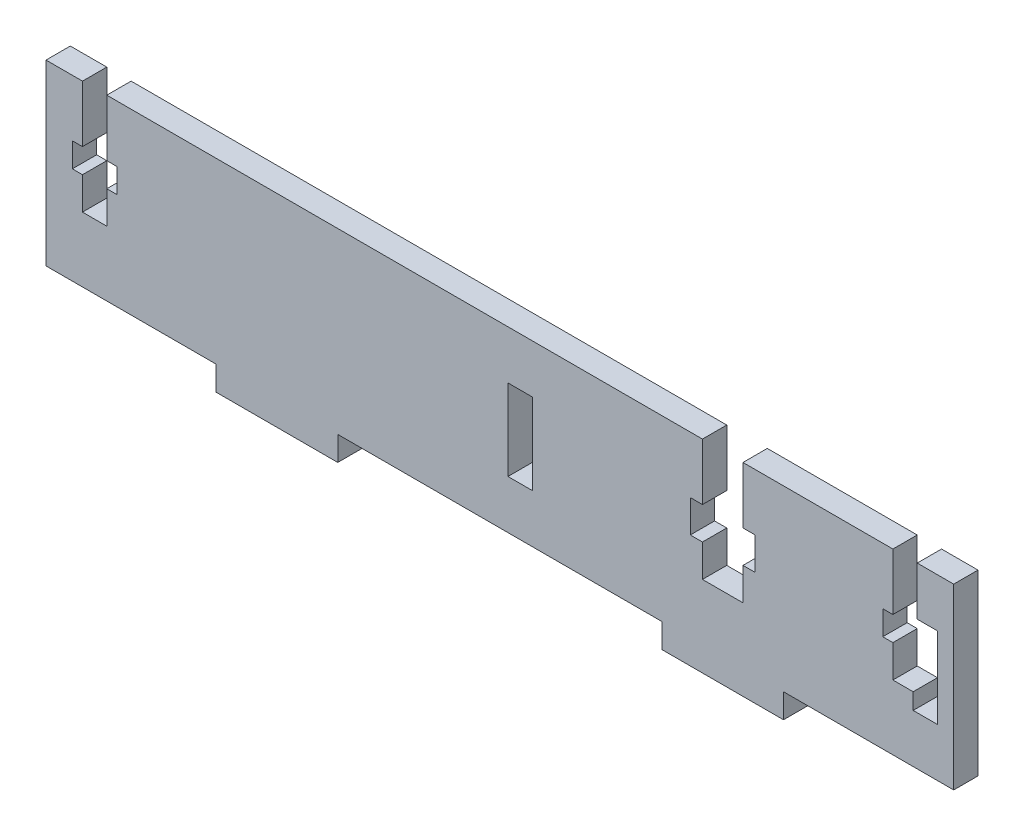
SolidWorks part; units mm, degrees
material "ABS PC"
ref_plane "Front Plane" through (0, 0, 0) normal (0, 0, 1) x (1, 0, 0)
ref_plane "Top Plane" through (0, 0, 0) normal (0, 1, 0) x (1, 0, 0)
ref_plane "Right Plane" through (0, 0, 0) normal (1, 0, 0) x (0, 0, -1)
sketch "Sketch1" plane through (0, 0, 0) normal (0, 0, 1) x (1, 0, 0)
  line L0 (-20, -11) -> (20, -11)
  line L1 (-56, 11) -> (56, 11)
  line L2 (-56, 11) -> (-56, -11)
  line L3 (-56, -11) -> (-35, -11)
  line L4 (56, 11) -> (56, -11)
  line L5 (35, -11) -> (56, -11)
  line L6 (-35, -11) -> (-35, -14)
  line L7 (-35, -14) -> (-20, -14)
  line L8 (-20, -11) -> (-20, -14)
  line L9 (0, 11) -> (0, 0) construction
  line L10 (20, -11) -> (20, -14)
  line L11 (20, -14) -> (35, -14)
  line L12 (35, -11) -> (35, -14)
  line L13 (0, 0) -> (0, -11) construction
  dimension "D1" = 22
  dimension "D2" = 112
  dimension "D3" = 15
  dimension "D4" = 3
  dimension "D5" = 40
extrude "Boss-Extrude1" add sketch "Sketch1" along normal mid plane 3 contours L1 L4 L5 L12 L11 L10 L0 L8 L7 L6 L3 L2
sketch "Sketch2" plane through (0, 0, 1.5) normal (0, 0, 1) x (1, 0, 0)
  line L0 (54, -5) -> (54, 5) construction
  line L1 (1, 5) -> (4, 5)
  line L2 (1, 5) -> (1, -5)
  line L3 (1, -5) -> (4, -5)
  line L4 (4, 5) -> (4, -5)
  line L5 (51, 5) -> (54, 5)
  line L6 (51, 5) -> (51, -5)
  line L7 (51, -5) -> (54, -5)
  line L8 (54, 5) -> (54, -5)
  line L9 (0, 0) -> (1, 0) construction
  dimension "D1" = 3
  dimension "D2" = 47
  dimension "D3" = 10
extrude "Cut-Extrude1" cut sketch "Sketch2" against normal through all
sketch "Sketch3" plane through (0, 0, 1.5) normal (0, 0, 1) x (1, 0, 0)
  line L0 (-56, 11) -> (56, 11) construction
  line L1 (15, 11) -> (40, 11)
  line L2 (15, 11) -> (15, 8)
  line L3 (15, 8) -> (40, 8)
  line L4 (40, 11) -> (40, 8)
  line L5 (27.5, -14) -> (27.5, 8) construction
  line L6 (20, -14) -> (35, -14) construction
  dimension "D1" = 25
  dimension "D2" = 3
extrude "Cut-Extrude2" [suppressed] cut sketch "Sketch3" against normal through all
sketch "Sketch4" plane through (0, 0, 1.5) normal (0, 0, 1) x (1, 0, 0)
  line L0 (25, 11) -> (25, 4)
  line L1 (-56, 11) -> (56, 11) construction
  line L2 (25, 4) -> (23.5, 4)
  line L3 (23.5, 4) -> (23.5, 0)
  line L4 (23.5, 0) -> (25, 0)
  line L5 (25, 0) -> (25, -4)
  line L6 (25, -4) -> (30, -4)
  line L7 (30, -4) -> (30, 0)
  line L8 (30, 0) -> (31.5, 0)
  line L9 (31.5, 0) -> (31.5, 4)
  line L10 (31.5, 4) -> (30, 4)
  line L11 (30, 4) -> (30, 11)
  line L12 (30, 11) -> (25, 11)
  line L13 (0, 11) -> (0, -11) construction
  line L14 (-20, -11) -> (20, -11) construction
  line L15 (-30, 11) -> (-25, 11)
  line L16 (-30, 4) -> (-30, 11)
  line L17 (-31.5, 4) -> (-30, 4)
  line L18 (-31.5, 0) -> (-31.5, 4)
  line L19 (-30, 0) -> (-31.5, 0)
  line L20 (-30, -4) -> (-30, 0)
  line L21 (-25, -4) -> (-30, -4)
  line L22 (-25, 0) -> (-25, -4)
  line L23 (-23.5, 0) -> (-25, 0)
  line L24 (-23.5, 4) -> (-23.5, 0)
  line L25 (-25, 4) -> (-23.5, 4)
  line L26 (-25, 11) -> (-25, 4)
  line L27 (-27.5, -4) -> (-27.5, 11) construction
  line L28 (27.5, -4) -> (27.5, 11) construction
  line L29 (4, 0) -> (27.5, 0) construction
  line L30 (4, -5) -> (4, 5) construction
  line L31 (27.5, 0) -> (51, 0) construction
  line L32 (51, 5) -> (51, -5) construction
  dimension "D1" = 5
  dimension "D2" = 8
  dimension "D3" = 4
  dimension "D4" = 15
extrude "Cut-Extrude3" cut sketch "Sketch4" against normal through all
ref_plane "Plane1" through (27.5, 0, 0) normal (-1, 0, 0) x (0, 0, 1)
ref_plane "Plane2" through (-27.5, 0, 0) normal (1, 0, 0) x (0, 0, -1)
sketch "Sketch5" plane through (0, 0, 1.5) normal (0, 0, 1) x (1, 0, 0)
  line L0 (-51.5, 11) -> (-51.5, 4)
  line L1 (-56, 11) -> (-30, 11) construction
  line L2 (-51.5, 4) -> (-52.75, 4)
  line L3 (-52.75, 4) -> (-52.75, 1)
  line L4 (-52.75, 1) -> (-51.5, 1)
  line L5 (-51.5, 1) -> (-51.5, -3)
  line L6 (-51.5, -3) -> (-48.5, -3)
  line L7 (-48.5, -3) -> (-48.5, 1)
  line L8 (-48.5, 1) -> (-47.25, 1)
  line L9 (-47.25, 1) -> (-47.25, 4)
  line L10 (-47.25, 4) -> (-48.5, 4)
  line L11 (-48.5, 4) -> (-48.5, 11)
  line L12 (-48.5, 11) -> (-51.5, 11)
  line L13 (-30, 4) -> (-31.5, 4) construction
  line L15 (48.5, 11) -> (51.5, 11)
  line L16 (-20, -11) -> (20, -11) construction
  line L17 (-25, 11) -> (25, 11) construction
  line L18 (0, 11) -> (0, 0) construction
  line L19 (0, 0) -> (0, -11) construction
  line L20 (48.5, 4) -> (48.5, 11)
  line L21 (47.25, 4) -> (48.5, 4)
  line L22 (47.25, 1) -> (47.25, 4)
  line L23 (48.5, 1) -> (47.25, 1)
  line L24 (48.5, -3) -> (48.5, 1)
  line L25 (51.5, -3) -> (48.5, -3)
  line L26 (51.5, 1) -> (51.5, -3)
  line L27 (52.75, 1) -> (51.5, 1)
  line L28 (52.75, 4) -> (52.75, 1)
  line L29 (51.5, 4) -> (52.75, 4)
  line L30 (51.5, 11) -> (51.5, 4)
  line L31 (-50, -3) -> (-50, 11) construction
  line L32 (50, -3) -> (50, 11) construction
  dimension "D1" = 3
  dimension "D2" = 100
  dimension "D3" = 5.5
  dimension "D4" = 3
  dimension "D5" = 14
extrude "Cut-Extrude4" cut sketch "Sketch5" against normal through all
ref_plane "Plane3" through (50, 0, 0) normal (-1, 0, 0) x (0, 0, 1)
ref_plane "Plane4" through (-50, 0, 0) normal (1, 0, 0) x (0, 0, -1)
ref_axis "Axis1" through (-50, -15.25, 0) along (0, 1, 0)
ref_axis "Axis2" through (50, 12.25, 0) along (0, -1, 0)
ref_axis "Axis3" through (27.5, 12.25, 0) along (0, -1, 0)
ref_axis "Axis4" through (-27.5, -15.25, 0) along (0, 1, 0)
sketch "Sketch6" plane through (0, 0, 1.5) normal (0, 0, 1) x (1, 0, 0)
  line L0 (-48.5, 11) -> (-30, 11) construction
  line L1 (-35.7572, 11) -> (-17.1907, 11)
  line L2 (-35.7572, 11) -> (-35.7572, -6.9332)
  line L3 (-35.7572, -6.9332) -> (-17.1907, -6.9332)
  line L4 (-17.1907, 11) -> (-17.1907, -6.9332)
extrude "Boss-Extrude3" add sketch "Sketch6" against normal through all
